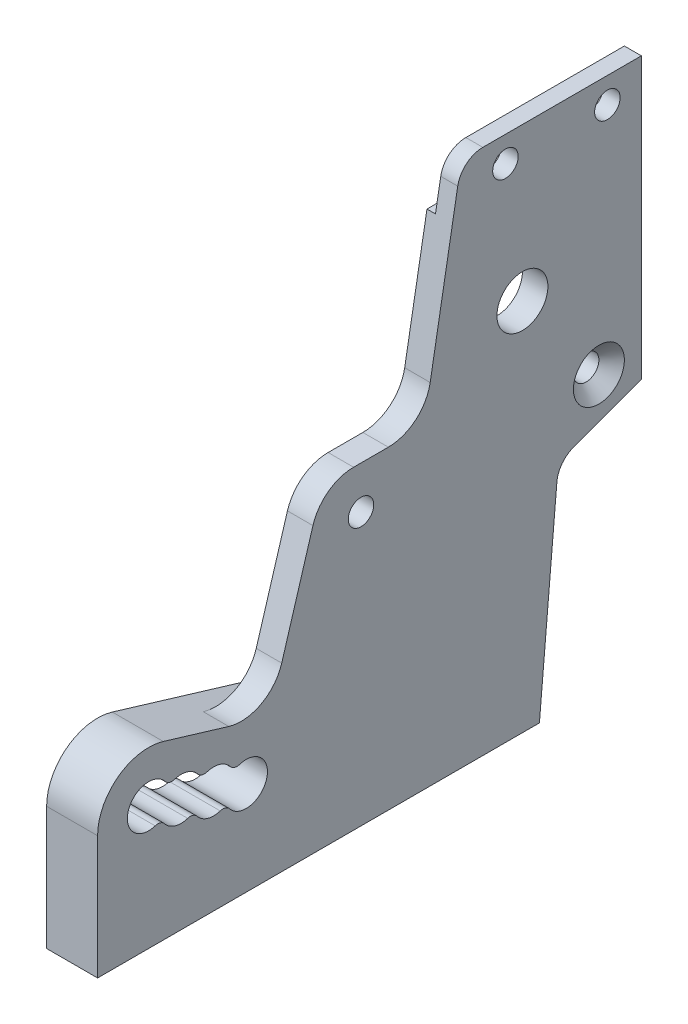
SolidWorks part; units mm, degrees
material "1060 Alloy"
ref_plane "Front Plane" through (0, 0, 0) normal (0, 0, 1) x (1, 0, 0)
ref_plane "Top Plane" through (0, 0, 0) normal (0, 1, 0) x (1, 0, 0)
ref_plane "Right Plane" through (0, 0, 0) normal (1, 0, 0) x (0, 0, -1)
sketch "Sketch1" plane through (0, 0, 0) normal (1, 0, 0) x (0, 0, -1)
  line L1 (0, 0) -> (64, 0)
  line L2 (0, 0) -> (0, 62)
  line L3 (0, 62) -> (64, 62)
  line L4 (64, 0) -> (64, 62)
  circle A0 centre (6, 14.5) radius 2.5
  circle A1 centre (50, 44) radius 3
  dimension "D1" = 6
  dimension "D2" = 5
  dimension "D3" = 14.5
  dimension "D4" = 6
  dimension "D5" = 44
  dimension "D6" = 50
  dimension "D7" = 64
  dimension "D8" = 62
extrude "Boss-Extrude1" add sketch "Sketch1" along normal blind 6
sketch "Sketch2" plane through (6, 0, 0) normal (1, 0, 0) x (0, 0, -1)
  line L0 (0, 62) -> (0, 0) construction
  line L1 (0, 0) -> (64, 0) construction
  line L2 (7.7322, 20.2445) -> (27.5931, 14.2555)
  line L4 (0, 14.5) -> (0, 63)
  line L5 (0, 63) -> (43, 63)
  line L6 (43, 63) -> (35.2342, 18.9581)
  line L7 (64, 62) -> (0, 62) construction
  arc A0 (0, 14.5) -> (7.7322, 20.2445) centre (6, 14.5) cw
  circle A1 centre (50, 44) radius 5 construction
  circle A2 centre (6, 14.5) radius 2.5 construction
  arc A4 (27.5931, 14.2555) -> (35.2342, 18.9581) centre (29.3254, 20) ccw
  dimension "D2" = 10
  dimension "D4" = 80
  dimension "D1" = 1
  dimension "D3" = 43
  dimension "D5" = 20
extrude "Cut-Extrude1" cut sketch "Sketch2" against normal up to next
sketch "Sketch3" plane through (6, 0, 0) normal (1, 0, 0) x (0, 0, -1)
  line L2 (0, 0) -> (64, 0) construction
  line L57 (64, 0) -> (52, 0)
  line L58 (64, 0) -> (64, 29)
  line L59 (64, 29) -> (54.2259, 25.4425)
  line L60 (52, 0) -> (54.2259, 25.4425)
  dimension "D1" = 52
  dimension "D2" = 29
  dimension "D3" = 70
  dimension "D4" = 85
extrude "Cut-Extrude2" cut sketch "Sketch3" against normal up to next
fillet "Fillet1" radius 3 1 edges at (3, 62, -42.8237)
fillet "Fillet2" radius 3 1 edges at (3, 25.4425, -54.2259)
hole_wizard "Tap Drill for M3 Tap1" positions "Sketch5" profile "Sketch4" hole size "M3" standard "ISO"
sketch "Sketch5" plane through (0, 0, 0) normal (0, -1, 0) x (-1, 0, 0)
  line L1 (-6, 0) -> (0, 0) construction
  line L2 (-6, 0) -> (-6, 52) construction
  point P0 (-3, 48)
  point P2 (-3, 12)
  dimension "D1" = 3
  dimension "D2" = 12
  dimension "D3" = 36
sketch "Sketch4" plane through (3, 0, -48) normal (1, 0, 0) x (0, 0, -1)
  line L0 (0, 0) -> (0, 9.7511)
  line L1 (0, 9.7511) -> (1.25, 9)
  line L2 (1.25, 9) -> (1.25, 0)
  line L5 (1.25, 0) -> (0, 0)
  line L10 (0, 9.7511) -> (-1.25, 9) construction
  line L11 (0, -6.35) -> (0, 107.95) construction
  dimension "Hole Dia." = 2.5
  dimension "Hole Depth" = 9
  dimension "Drill Angle" = 118
sketch "Sketch9" plane through (0, 0, 0) normal (-1, 0, 0) x (0, 0, 1)
  line L0 (-64, 62) -> (-64, 37)
  line L1 (-64, 62) -> (-45.341, 62) construction
  line L3 (-64, 29) -> (-64, 62) construction
  line L4 (-64, 62) -> (-42, 62)
  line L5 (-42, 62) -> (-33.6499, 15.8408)
  line L6 (-54, 37) -> (-64, 37)
  line L12 (-33.6499, 15.8408) -> (-54, 37)
  arc A0 (-35.2342, 18.9581) -> (-27.5931, 14.2555) centre (-29.3254, 20) ccw construction
  dimension "D1" = 10
  dimension "D2" = 25
  dimension "D3" = 22
extrude "Cut-Extrude3" cut sketch "Sketch9" against normal blind 3
sketch "Sketch10" plane through (3, 0, 0) normal (-1, 0, 0) x (0, 0, 1)
  line L0 (-45.341, 62) -> (-64, 62) construction
  line L1 (-64, 62) -> (-64, 37) construction
  circle A0 centre (-60, 59) radius 1.5
  circle A1 centre (-48, 59) radius 1.5
  dimension "D1" = 3
  dimension "D2" = 3
  dimension "D3" = 4
  dimension "D4" = 12
extrude "Cut-Extrude4" cut sketch "Sketch10" against normal up to next
sketch "Sketch11" plane through (0, 0, 0) normal (-1, 0, 0) x (0, 0, 1)
  line L0 (-6, 14.5) -> (-25.8609, 8.511) construction
  line L1 (-7.7322, 20.2445) -> (-27.5931, 14.2555) construction
  circle A0 centre (-9.8297, 13.3452) radius 2.5
  circle A1 centre (-6, 14.5) radius 2.5 construction
  dimension "D1" = 4
extrude "Cut-Extrude5" cut sketch "Sketch11" against normal up to next
pattern_linear "LPattern1" count 3 spacing 4 along (0, -0.2887, -0.9574) of "Cut-Extrude5"
fillet "Fillet3" radius 1 6 edges at (3, 12.4865, -7.4818) (3, 11.3316, -11.3114) (3, 10.1768, -15.1411) (3, 15.3587, -8.3479) (3, 14.2039, -12.1776) (3, 13.0491, -16.0072)
sketch "Sketch12" plane through (3, 0, 0) normal (-1, 0, 0) x (0, 0, 1)
  line L1 (-64, 62) -> (-41.0174, 62)
  line L2 (-64, 62) -> (-64, 56)
  line L3 (-64, 56) -> (-41.0174, 56)
  line L4 (-41.0174, 62) -> (-41.0174, 56)
  dimension "D1" = 6
extrude "Cut-Extrude6" cut sketch "Sketch12" against normal blind 1
sketch "Sketch13" plane through (0, 0, 0) normal (-1, 0, 0) x (0, 0, 1)
  line L1 (-64, 29) -> (-54, 29)
  line L2 (-64, 29) -> (-64, 35)
  line L3 (-64, 35) -> (-54, 35)
  line L4 (-54, 29) -> (-54, 35)
  dimension "D1" = 6
  dimension "D2" = 10
extrude "Cut-Extrude7" cut sketch "Sketch13" against normal blind 1
sketch "Sketch14" plane through (6, 0, 0) normal (1, 0, 0) x (0, 0, -1)
  line L0 (38.4155, 37) -> (34.0611, 12.3051)
  line L1 (35.2342, 18.9581) -> (42.3865, 59.5209) construction
  line L2 (34.0611, 12.3051) -> (20.2268, 16.4768)
  line L3 (7.7322, 20.2445) -> (27.5931, 14.2555) construction
  line L4 (20.2268, 16.4768) -> (26.4155, 37)
  line L5 (26.4155, 37) -> (38.4155, 37)
  line L6 (64, 62) -> (45.341, 62) construction
  line L7 (0, 14.5) -> (0, 0) construction
  line L8 (0, 0) -> (52, 0) construction
  circle A0 centre (31, 32) radius 1.5
  dimension "D5" = 3
  dimension "D1" = 25
  dimension "D2" = 12
  dimension "D3" = 31
  dimension "D4" = 32
extrude "Boss-Extrude2" add sketch "Sketch14" against normal up to surface (3 mm away) up to face at (3, 44, -53)
fillet "Fillet4" radius 5 3 edges at (4.5, 37, -26.4155) (4.5, 16.4768, -20.2268) (4.5, 37, -38.4155)
sketch "Sketch15" plane through (1, 0, 0) normal (-1, 0, 0) x (0, 0, 1)
  line L0 (-54, 35) -> (-64, 35) construction
  line L1 (-54, 29) -> (-54, 35) construction
  circle A0 centre (-59, 32) radius 1.5
  dimension "D1" = 3
  dimension "D2" = 3
  dimension "D3" = 5
extrude "Cut-Extrude8" cut sketch "Sketch15" against normal up to next
chamfer "Chamfer1" distance 1.5 angle 45 1 edges at (6, 32, -57.5)
sketch "Sketch16" plane through (0, 0, 0) normal (-1, 0, 0) x (0, 0, 1)
  line L0 (-54, 37) -> (-40.783, 18.7148)
  line L1 (-27.5931, 14.2555) -> (-15.4397, 17.9203) construction
  line L2 (-54, 37) -> (-27.5931, 14.2555)
  arc A0 (-40.783, 18.7148) -> (-27.5931, 14.2555) centre (-31.0576, 25.7445) ccw
  dimension "D1" = 12
extrude "Cut-Extrude9" cut sketch "Sketch16" against normal up to surface (3 mm away) up to face at (3, 33.4674, -37.6696)
